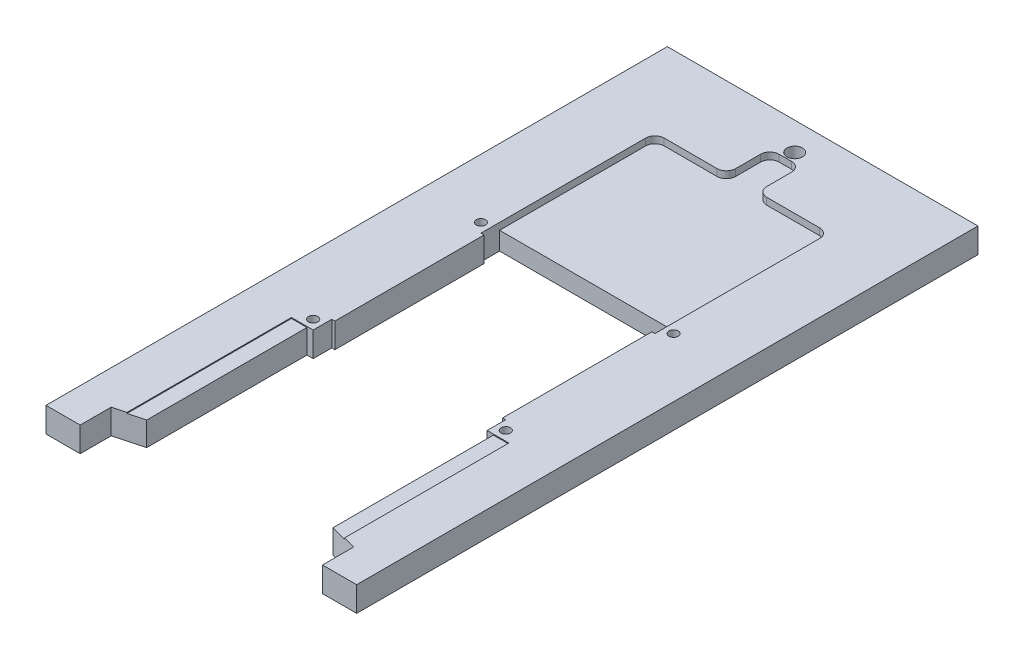
SolidWorks part; units mm, degrees
ref_plane "Front Plane" through (0, 0, 0) normal (0, 0, 1) x (1, 0, 0)
ref_plane "Top Plane" through (0, 0, 0) normal (0, 1, 0) x (1, 0, 0)
ref_plane "Right Plane" through (0, 0, 0) normal (1, 0, 0) x (0, 0, -1)
sketch "Sketch1" plane through (0, 0, 0) normal (0, 1, 0) x (1, 0, 0)
  line L1 (-30, 12.4115) -> (-30, 64)
  line L2 (-28, 124) -> (28, 124)
  line L3 (30, 64) -> (30, 12.4115)
  line L6 (-50, 0) -> (-39, 0)
  line L8 (-28, 70) -> (-28, 64)
  line L9 (-28, 64) -> (-30, 64)
  line L10 (28, 70) -> (28, 64)
  line L11 (28, 64) -> (30, 64)
  line L12 (-28, 70) -> (-27, 70)
  line L13 (-27, 70) -> (-27, 118)
  line L14 (-27, 118) -> (-28, 118)
  line L15 (-28, 118) -> (-28, 124)
  line L16 (28, 124) -> (28, 118)
  line L17 (28, 118) -> (27, 118)
  line L18 (27, 118) -> (27, 70)
  line L19 (27, 70) -> (28, 70)
  line L20 (-39, 0) -> (-39, 10)
  line L21 (-39, 10) -> (-30, 12.4115)
  line L22 (39, 0) -> (39, 10)
  line L23 (39, 10) -> (30, 12.4115)
  line L24 (-50, 0) -> (-50, 200)
  line L25 (-50, 200) -> (50, 200)
  line L26 (50, 200) -> (50, 0)
  line L27 (50, 0) -> (39, 0)
  circle A0 centre (-31, 67) radius 1.5
  circle A1 centre (31, 67) radius 1.5
  circle A2 centre (-31, 121) radius 1.5
  circle A3 centre (31, 121) radius 1.5
  dimension "D17" = 3
  dimension "D2" = 60
  dimension "D3" = 67
  dimension "D5" = 60
  dimension "D6" = 56
  dimension "D7" = 6
  dimension "D8" = 1
  dimension "D9" = 78
  dimension "D10" = 10
  dimension "D11" = 105
  dimension "D12" = 100
  dimension "D13" = 200
  dimension "D14" = 50
  dimension "D16" = 62
  dimension "D18" = 54
  dimension "D19" = 3
  dimension "D20" = 3
extrude "Boss-Extrude1" add sketch "Sketch1" along normal blind 8
sketch "Sketch2" plane through (0, 8, 0) normal (0, 1, 0) x (1, 0, 0)
  line L1 (-28, 124) -> (28, 124)
  line L2 (-28, 124) -> (-28, 174)
  line L3 (-28, 174) -> (28, 174)
  line L4 (28, 124) -> (28, 174)
  dimension "D1" = 50
extrude "Cut-Extrude1" cut sketch "Sketch2" against normal blind 2.2
sketch "Sketch3" plane through (0, 8, 0) normal (0, 1, 0) x (1, 0, 0)
  line L0 (28, 174) -> (-28, 174) construction
  line L1 (-5, 174) -> (5, 174)
  line L2 (-5, 174) -> (-5, 188)
  line L3 (-5, 188) -> (5, 188)
  line L4 (5, 174) -> (5, 188)
  line L5 (-28, 174) -> (-28, 124) construction
  dimension "D1" = 10
  dimension "D2" = 23
  dimension "D3" = 14
extrude "Cut-Extrude2" cut sketch "Sketch3" against normal up to surface (2.2 mm away) up to face at (0, 5.8, -149)
sketch "Sketch4" plane through (0, 8, 0) normal (0, 1, 0) x (1, 0, 0)
  line L0 (-5, 174) -> (-28, 174) construction
  circle A0 centre (0, 191) radius 2.5
  dimension "D1" = 5
  dimension "D2" = 17
extrude "Cut-Extrude3" cut sketch "Sketch4" against normal up to next
fillet "Fillet1" radius 3 6 edges at (28, 6.9, -174) (-28, 6.9, -174) (5, 6.9, -174) (-5, 6.9, -174) (5, 6.9, -188) (-5, 6.9, -188)
sketch "Sketch5" plane through (0, 0, 0) normal (0, -1, 0) x (1, 0, 0)
  circle A0 centre (-31, -67) radius 2.75
  circle A1 centre (31, -67) radius 2.75
  circle A2 centre (-31, -121) radius 2.75
  circle A3 centre (31, -121) radius 2.75
  dimension "D1" = 5.5
extrude "Cut-Extrude4" cut sketch "Sketch5" against normal blind 3
chamfer "Chamfer1" distance 1.25 angle 40 4 edges at (31, 3, -68.5) (31, 3, -122.5) (-31, 3, -122.5) (-31, 3, -68.5) first distance on face at (31, 3, -68.5) first distance on face at (31, 3, -122.5) first distance on face at (-31, 3, -122.5) first distance on face at (-31, 3, -68.5)
sketch "Sketch6" plane through (0, 8, 0) normal (0, 1, 0) x (1, 0, 0)
  line L0 (-30, 64) -> (-28, 64) construction
  line L1 (-35, 64) -> (35, 64)
  line L2 (-35, 64) -> (-35, 0)
  line L3 (-35, 0) -> (35, 0)
  line L4 (35, 64) -> (35, 0)
  line L5 (-50, 0) -> (-39, 0) construction
  line L6 (-30, 12.4115) -> (-30, 64) construction
  line L7 (30, 64) -> (30, 12.4115) construction
  dimension "D1" = 5
  dimension "D2" = 5
extrude "Cut-Extrude5" cut sketch "Sketch6" against normal blind 0.3
